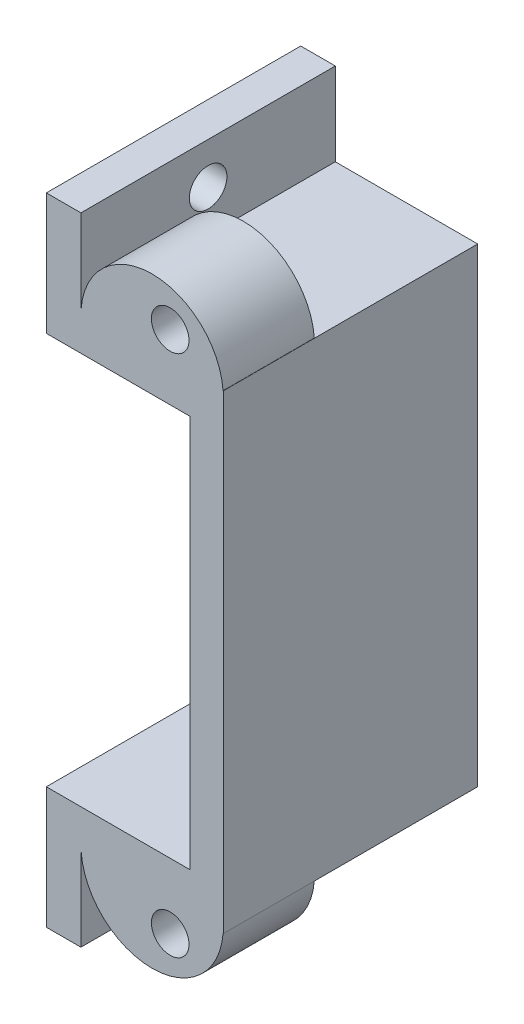
SolidWorks part; units mm, degrees
ref_plane "Front Plane" through (0, 0, 0) normal (0, 0, 1) x (1, 0, 0)
ref_plane "Top Plane" through (0, 0, 0) normal (0, 1, 0) x (1, 0, 0)
ref_plane "Right Plane" through (0, 0, 0) normal (1, 0, 0) x (0, 0, -1)
sketch "Sketch1" plane through (0, 0, 0) normal (0, 0, 1) x (1, 0, 0)
  line L0 (13, -18) -> (16, -18)
  line L1 (-13, -18) -> (13, -18) construction
  line L2 (-13, -18) -> (-13, 18) construction
  line L3 (-13, 18) -> (13, 18) construction
  line L4 (13, -18) -> (13, 18) construction
  line L5 (-13, -18) -> (13, 18) construction
  line L6 (-13, 18) -> (13, -18) construction
  line L7 (16, -18) -> (16, 21)
  line L8 (16, 21) -> (0, 21)
  line L10 (-13, 18) -> (13, 18)
  line L11 (13, 18) -> (13, -18)
  line L12 (0, 18) -> (0, 21) construction
  line L13 (3.1271, 18) -> (3.1271, 21)
  line L14 (9.5636, 18) -> (9.5636, 27.4364) construction
  line L15 (0, 21) -> (0, 28.5)
  line L16 (0, 18) -> (0, 21)
  line L17 (3.1271, 21) -> (3.1271, 28.5)
  line L18 (3.1271, 28.5) -> (0, 28.5)
  line L19 (0, -18) -> (0, -21)
  line L20 (0, -21) -> (16, -21)
  line L21 (16, -21) -> (16, -18)
  line L22 (13, -18) -> (0, -18)
  line L23 (3.1271, -18) -> (3.1271, -28.5)
  line L24 (3.1271, -28.5) -> (0, -28.5)
  line L25 (0, -28.5) -> (0, -21)
  line L26 (11.328, 21) -> (11.328, 18)
  arc A0 (3.1271, 21) -> (16, 21) centre (9.5636, 21) cw
  point P0 (0, 0)
  dimension "D1" = 26
  dimension "D2" = 36
  dimension "D3" = 3
  dimension "D4" = 3
  dimension "D5" = 7.5
  dimension "D6" = 3
  dimension "D7" = 10.5
extrude "Boss-Extrude1" add sketch "Sketch1" along normal blind 23 contours L13 L10 L11 L0 L7 L8 | L17 L18 L15 L8 | L16 L10 L13 L8 | L25 L24 L23 L20 | L23 L22 L19 L20 | L22 L23 L20 L21 L0 | A0 L8 | L26 L8 L13 L10 region at (14.404, 2.24, 0) region at (9.5636, -19.5, 0) region at (1.5636, -19.5, 0) region at (9.5636, 23.7317, 0) region at (7.2275, 19.5, 0) region at (1.5636, -24.75, 0) region at (1.5636, 19.5, 0) region at (1.5636, 24.75, 0)
sketch "Sketch2" plane through (3.1271, 0, 0) normal (1, 0, 0) x (0, 0, -1)
  line L0 (-23, 28.5) -> (0, 21) construction
  line L1 (0, 21) -> (0, 28.5) construction
  line L2 (0, 28.5) -> (-23, 21) construction
  line L3 (-14.75, 24.75) -> (-14.75, 28.5)
  line L4 (-23, 28.5) -> (0, 28.5) construction
  line L5 (-8.25, 24.75) -> (-8.25, 28.5)
  line L6 (-14.75, 28.5) -> (-8.25, 28.5)
  line L7 (-11.5, 21.5) -> (0, 21.5)
  line L8 (-11.5, 21.5) -> (-14.75, 21.5)
  line L9 (-14.75, 21.5) -> (-14.75, 24.75)
  circle A0 centre (-11.5, 24.75) radius 1.7
  circle A1 centre (-11.5, 24.75) radius 3.25
  point P12 (-11.5, 24.75)
  line M4 (0, 21) -> (0, 28.5)
  line M5 (0, 28.5) -> (-23, 28.5)
  dimension "D1" = 3.4
  dimension "D2" = 6.5
extrude "Cut-Extrude1" cut sketch "Sketch2" against normal through all and the other way through all contours A0
extrude "Cut-Extrude5" cut sketch "Sketch2<8>" along normal blind 23 contours A1 L5 L3 M5 | A1 A0 | A1 L9 L8 | A1 L7 L5 M4 M5 region at (3.1271, 22.2259, 14.0241) region at (3.1271, 26.625, 14.675) region at (3.1271, 27.9081, 11.5) region at (3.1271, 24.8952, 4.3082)
sketch "Sketch2<8>" plane through (3.1271, 0, 0) normal (1, 0, 0) x (0, 0, -1) same geometry as "Sketch2"
ref_plane "Plane1" through (0, 0.25, 0) normal (0, -1, 0) x (-1, 0, 0)
mirror "Mirror5" about plane through (0, 0.25, 0) normal (0, -1, 0) of "Cut-Extrude1", "Boss-Extrude1", "Cut-Extrude5"
sketch "Sketch5" plane through (0, 0, 23) normal (0, 0, 1) x (1, 0, 0)
  line L0 (15.9805, 21.5) -> (3.1271, 21.5)
  line L1 (13, 18) -> (13, 26.4423)
  arc A0 (15.9805, 21.5) -> (3.1466, 21.5) centre (9.5636, 21) ccw construction
  circle A1 centre (11.2, 23.9) radius 1.7
  dimension "D1" = 3.4
  dimension "D2" = 1.8
  dimension "D3" = 2.4
extrude "Cut-Extrude6" cut sketch "Sketch5" against normal through all contours A1 region at (11.2, 23.9, 23)
mirror "Mirror8" about plane through (0, 0.25, 0) normal (0, -1, 0) of "Cut-Extrude6"
sketch "Sketch6" plane through (3.1271, 0, 0) normal (1, 0, 0) x (0, 0, -1)
  line L0 (-23, 29) -> (0, 21.5)
  line L1 (0, 29) -> (-23, 21.5)
  circle A1 centre (-11.5, 25.25) radius 1.7
  dimension "D1" = 3.4
extrude "Cut-Extrude7" cut sketch "Sketch6" against normal blind 23 contours L1 A1 L0 | L1 A1 L0 | L0 A1 L1 | L0 A1 L1 region at (3.1271, 26.1082, 11.5) region at (3.1271, 25.25, 12.6147) region at (3.1271, 25.25, 10.3853) region at (3.1271, 24.3918, 11.5)
